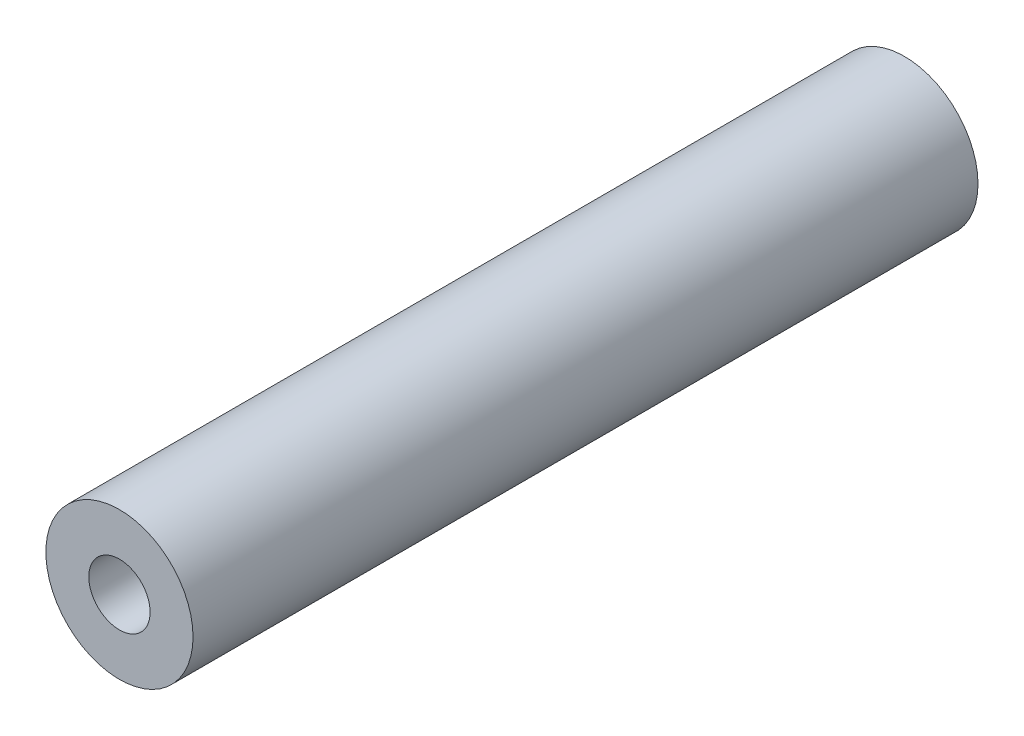
SolidWorks part; units mm, degrees
ref_plane "Front Plane" through (0, 0, 0) normal (0, 0, 1) x (1, 0, 0)
ref_plane "Top Plane" through (0, 0, 0) normal (0, 1, 0) x (1, 0, 0)
ref_plane "Right Plane" through (0, 0, 0) normal (1, 0, 0) x (0, 0, -1)
sketch "Sketch1" plane through (0, 0, 0) normal (0, 0, 1) x (1, 0, 0)
  circle A0 centre (0, 0) radius 3
  dimension "D1" = 6
extrude "Boss-Extrude1" add sketch "Sketch1" along normal blind 32
hole_wizard "M3 Tapped Hole1" positions "Sketch2" profile "Sketch3" tap size "M3" standard "ISO" end condition up to next
sketch "Sketch2" plane through (0, 0, 32) normal (0, 0, 1) x (1, 0, 0)
  point P0 (0, 0)
cosmetic thread "Hole Thread1" parameters "D2"=3
sketch "Sketch3" plane through (0, 0, 32) normal (1, 0, 0) x (0, -1, 0)
  line L0 (0, 0) -> (0, 32)
  line L1 (0, 32) -> (1.25, 32)
  line L2 (1.25, 32) -> (1.25, 0)
  line L5 (1.25, 0) -> (0, 0)
  line L11 (0, -6.35) -> (0, 107.95) construction
  dimension "Thru Tap Drill Dia." = 2.5
  dimension "Thru Tap Drill Depth" = 32
equation "\"roller_radius\"= 6.5"
equation "\"eccentricity\"= \"roller_radius\" * 0.325"
equation "\"outer_radius\"= 40"
equation "\"eccentric_shaft_radius\"= 16"
equation "\"rotor_width\"= 10"
equation "\"housing_depth\"= 40"
equation "\"bottom_depth\"= 5"
equation "\"roller_bearing_OD\"= \"roller_radius\" * 2"
equation "\"roller_bearing_ID\"= 6"
equation "\"eccentric_bearing_ID\"= 6"
equation "\"eccentric_bearing_OD\"= 15"
equation "\"roller_bearing_height\"= 5"
equation "\"eccentric_bearing_height\"= 5"
equation "\"bottom_bearing_ID\"= 15"
equation "\"bottom_bearing_OD\"= 32"
equation "\"bottom_bearing_height\"= 9"
equation "\"distance_to_output_rotor_holes\"= 20"
equation "\"D1@Sketch1\"=\"roller_bearing_ID\""
equation "\"output_bearing_ID\" = 25"
equation "\"output_bearing_OD\" = 37"
equation "\"output_bearing_height\" = 7"
equation "\"number_of_rollers\" = 15"
equation "\"housing_height\" = 27"
equation "\"spacer_1\" = 7"
equation "\"spacer_2\" = 2.5"
equation "\"spacer_3\" = 7.5"
equation "\"roller_pin_depth\" = 5"
equation "\"D1@Boss-Extrude1\"=\"eccentric_bearing_height\"+\"spacer_1\"+\"spacer_2\"+\"spacer_3\"+\"roller_bearing_height\"*2"
